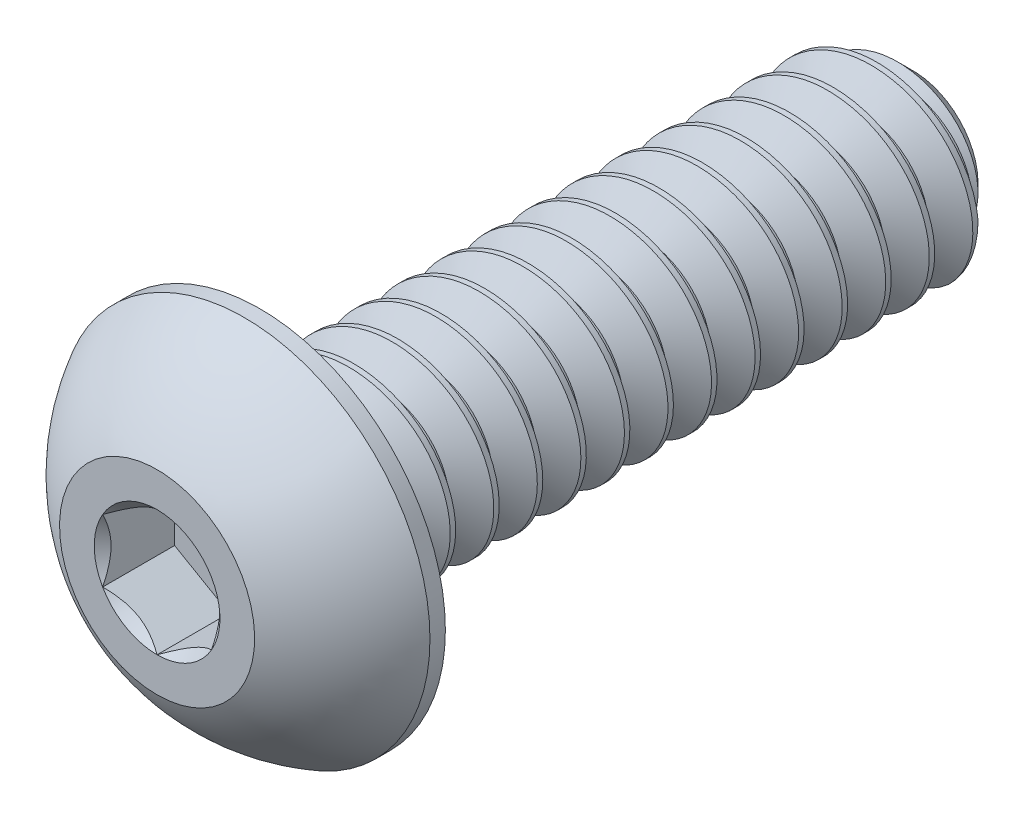
SolidWorks part; units mm, degrees
ref_plane "Front" through (0, 0, 0) normal (0, 0, 1) x (1, 0, 0)
ref_plane "Top" through (0, 0, 0) normal (0, 1, 0) x (1, 0, 0)
ref_plane "Right" through (0, 0, 0) normal (1, 0, 0) x (0, 0, -1)
sketch "Sketch1" plane through (0, 0, 0) normal (1, 0, 0) x (0, 0, -1)
  line L2 (1.4986, 1.4224) -> (11.0236, 1.4224) construction
  line L3 (11.0236, 1.4224) -> (11.0236, 0) construction
  line L4 (11.0236, 0) -> (1.4986, 0) construction
  line L6 (1.2738, 2.7051) -> (1.4986, 2.7051) construction
  line L7 (11.0236, 1.4224) -> (11.0236, -1.4224) construction
  line L8 (0, 0) -> (1.4986, 0) construction
  line L9 (1.4986, 2.7051) -> (1.4986, -2.7051) construction
  line L11 (1.4986, 1.4224) -> (1.4986, 0) construction
  line L13 (0, 0.7938) -> (0, -0.7938) construction
  line L14 (0, 0.7938) -> (0, 1.4224) construction
  arc A3 (0, 1.4224) -> (1.2738, 2.7051) centre (2.7151, 0) cw construction
  point P10 (9.4361, -1.4224)
  dimension "D1" = 0.2248
  dimension "D2" = 1.5875
sketch "Sketch11" plane through (0, 0, 0) normal (1, 0, 0) x (0, 0, -1)
  line L1 (1.4986, 0) -> (11.0236, 0)
  line L4 (1.4986, 1.4224) -> (11.0236, 1.4224) construction
  line L5 (11.0236, 1.4224) -> (11.0236, 0) construction
  line L8 (1.4986, 1.4224) -> (11.0236, 1.4224)
  line L9 (11.0236, 1.4224) -> (11.0236, 0)
  line L10 (1.4986, 1.4224) -> (1.4986, 0)
revolve "Revolve1" add sketch "Sketch11" angle 360 about L1
chamfer "Chamfer1" distance 0.4763 angle 45 1 edges at (0, -1.4224, -11.0236)
sketch "Sketch7" plane through (0, 0, 0) normal (1, 0, 0) x (0, 0, -1)
  line L6 (1.2738, 2.7051) -> (1.4986, 2.7051) construction
  line L8 (0, 0) -> (1.4986, 0) construction
  line L11 (1.4986, 2.7051) -> (1.4986, -2.7051) construction
  line L12 (1.2738, 2.7051) -> (1.4986, 2.7051)
  line L13 (0, 0) -> (1.4986, 0)
  line L14 (0, 0.7938) -> (0, -0.7938) construction
  line L15 (1.4986, 2.7051) -> (1.4986, 0)
  line L16 (0, 1.4224) -> (0, 0)
  arc A2 (1.2738, 2.7051) -> (0, 1.4224) centre (2.7151, 0) ccw construction
  arc A3 (1.2738, 2.7051) -> (0, 1.4224) centre (2.7151, 0) ccw
revolve "Revolve2" add sketch "Sketch7" angle 360 mid plane about L13
sketch "Sketch5" plane through (0, 0, 0) normal (0, 0, 1) x (1, 0, 0)
  line L1 (0.7938, -0.4583) -> (0.7938, 0.4583)
  line L2 (0.7938, 0.4583) -> (0, 0.9165)
  line L3 (0, 0.9165) -> (-0.7937, 0.4583)
  line L4 (-0.7937, 0.4583) -> (-0.7937, -0.4583)
  line L5 (-0.7937, -0.4583) -> (0, -0.9165)
  line L6 (0, -0.9165) -> (0.7938, -0.4583)
  circle A0 centre (0, 0) radius 0.7938 construction
extrude "Cut-Extrude2" cut sketch "Sketch5" against normal blind 1.049
sketch "Sketch6" plane through (0, 0, 0) normal (0, 0, 1) x (1, 0, 0)
  circle A0 centre (0, 0) radius 0.9165
extrude "Cut-Extrude3" cut sketch "Sketch6" against normal blind 1.049 draft 45
sketch "Sketch3" plane through (0, 0, -11.0236) normal (0, 0, -1) x (-1, 0, 0)
  circle A0 centre (0, 0) radius 1.4224
curve "Helix/Spiral1" pitch 0.635 height 10.16 radius 1.4224 centre (0, 0, -11.0236) axis (0, 0, 1) start towards (0, 1, 0)
sketch "Sketch2" plane through (0, 0, 0) normal (1, 0, 0) x (0, 0, -1)
  line L0 (11.0236, 1.4224) -> (11.5792, 1.4224)
  line L1 (11.5792, 1.4224) -> (11.3411, 1.01)
  line L2 (11.3411, 1.01) -> (11.2617, 1.01)
  line L3 (11.2617, 1.01) -> (11.0236, 1.4224)
  line L4 (11.1427, 1.2162) -> (11.4602, 1.2162) construction
  dimension "D1" = 60
  dimension "D2" = 0.0794
  dimension "D3" = 0.3175
sweep "Cut-Sweep1" cut profiles "Sketch2" path "Helix/Spiral1"
sketch "Sketch9" [suppressed] plane through (0, 0, -6.731) normal (0, 0, 1) x (1, 0, 0)
  circle A2 centre (0, 0) radius 6.35
extrude "Boss-Extrude2" [suppressed] add sketch "Sketch9" against normal offset from surface (69.85 mm away) 31.75 up to face at (0, -0.9462, -11.0236)
ref_axis "Center Axis 1" through (0, 0, -10.5474) along (0, 0, 1)
ref_plane "Contact Plane 1" through (0, 0, -1.4986) normal (0, 0, -1) x (-1, 0, 0)
ref_plane "Contact Plane 2" through (0, 0, -11.0236) normal (0, 0, -1) x (-1, 0, 0)
equation "\"D3@Helix/Spiral1\" = \"Lg@Sketch1\" + \"D4@Helix/Spiral1\""
equation "\"D2@Sketch2\" = \"D4@Helix/Spiral1\" * .125"
equation "\"D3@Sketch2\" = \"D4@Helix/Spiral1\" * .5"
equation "\"D1@Chamfer1\" = \"D4@Helix/Spiral1\" * .75"
equation "\"D1@Cut-Extrude2\" = \"Head Ht@Sketch1\" * .7"
equation "\"D1@Sketch1\" = \"Head Ht@Sketch1\" * .15"
equation "\"D1@Cut-Extrude3\" = \"D1@Cut-Extrude2\""
equation "\"D1@Chamfer1\"=\"D4@Helix/Spiral1\" * .75"
equation "\"D2@Sketch1\"=\"D4@Helix/Spiral1\"*2.5"
